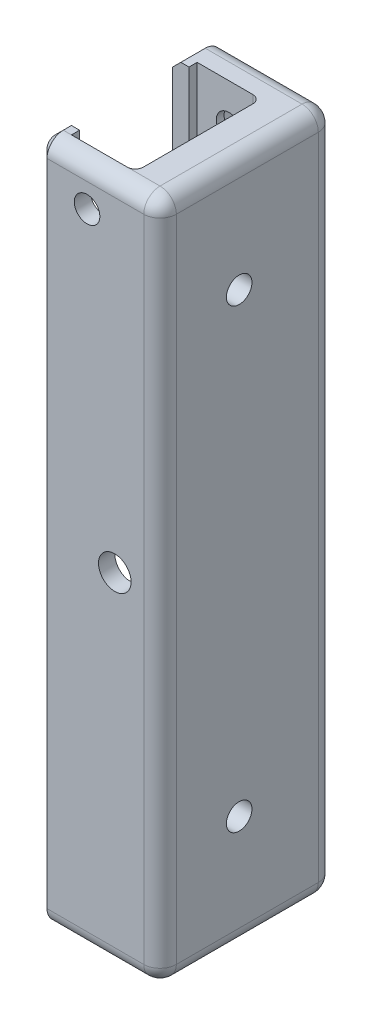
SolidWorks part; units mm, degrees
ref_plane "Front Plane" through (0, 0, 0) normal (0, 0, 1) x (1, 0, 0)
ref_plane "Top Plane" through (0, 0, 0) normal (0, 1, 0) x (1, 0, 0)
ref_plane "Right Plane" through (0, 0, 0) normal (1, 0, 0) x (0, 0, -1)
sketch "Sketch1" plane through (0, 0, 0) normal (0, 1, 0) x (1, 0, 0)
  line L0 (14.225, -12.25) -> (14.225, 12.25)
  line L1 (-6.225, -12.25) -> (6.225, -12.25) construction
  line L2 (-6.225, -12.25) -> (-6.225, 12.25) construction
  line L3 (-6.225, 12.25) -> (6.225, 12.25) construction
  line L4 (6.225, -12.25) -> (6.225, 12.25) construction
  line L5 (-6.225, -12.25) -> (6.225, 12.25) construction
  line L6 (-6.225, 12.25) -> (6.225, -12.25) construction
  line L7 (-6.225, 18.6) -> (6.225, 18.6)
  line L8 (-9.4, -15.425) -> (6.225, -15.425)
  line L9 (-9.4, -15.425) -> (-9.4, 12.25)
  line L10 (-9.4, 12.25) -> (-9.4, 18.6)
  line L11 (-9.4, 18.6) -> (-6.225, 18.6)
  line L12 (6.225, 18.6) -> (14.225, 18.6)
  line L13 (14.225, 18.6) -> (14.225, 12.25)
  line L14 (6.225, -15.425) -> (14.225, -15.425)
  line L15 (14.225, -15.425) -> (14.225, -12.25)
  point P0 (0, 0)
  dimension "D1" = 12.45
  dimension "D2" = 24.5
  dimension "D3" = 8
  dimension "D4" = 6.35
  dimension "D5" = 3.175
extrude "Boss-Extrude1" add sketch "Sketch1" along normal mid plane 133
sketch "Sketch2" plane through (0, 66.5, 0) normal (0, 1, 0) x (1, 0, 0)
  line L0 (14.225, 18.6) -> (-9.4, 18.6) construction
  line L1 (-6.225, -12.25) -> (6.225, -12.25)
  line L2 (-6.225, -12.25) -> (-6.225, 12.25)
  line L3 (-6.225, 12.25) -> (6.225, 12.25)
  line L4 (6.225, -12.25) -> (6.225, 12.25)
  line L5 (14.225, -15.425) -> (14.225, 18.6) construction
  line L6 (-9.4, -15.425) -> (14.225, -15.425) construction
  line L7 (-9.4, 18.6) -> (-9.4, -15.425) construction
  dimension "D1" = 6.35
  dimension "D2" = 8
  dimension "D3" = 3.175
  dimension "D4" = 3.175
extrude "Cut-Extrude1" cut sketch "Sketch2" against normal offset from surface (120.5 mm away) 54 up to plane "Top Plane" offset beyond the face yes
sketch "Sketch3" plane through (-9.4, 0, 0) normal (-1, 0, 0) x (0, 0, 1)
  line L0 (-18.6, 66.5) -> (15.425, 66.5) construction
  line L1 (10.6625, -50) -> (-10.6625, -50)
  line L2 (10.6625, -50) -> (10.6625, 66.5)
  line L3 (10.6625, 66.5) -> (-10.6625, 66.5)
  line L4 (-10.6625, -50) -> (-10.6625, 66.5)
  line L6 (15.425, 66.5) -> (15.425, -66.5) construction
  line L7 (-18.6, 66.5) -> (-18.6, -66.5) construction
  dimension "D1" = 50
  dimension "D2" = 4.7625
  dimension "D3" = 7.9375
extrude "Cut-Extrude2" cut sketch "Sketch3" against normal up to next
fillet "Fillet1" radius 1.5875 2 edges at (6.225, 6.25, 12.25) (6.225, 6.25, -12.25)
sketch "Sketch4" plane through (0, -66.5, 0) normal (0, -1, 0) x (1, 0, 0)
  line L1 (3.9687, 11.1125) -> (-3.9688, 11.1125)
  line L2 (3.9687, 11.1125) -> (3.9688, -11.1125)
  line L3 (3.9688, -11.1125) -> (-3.9687, -11.1125)
  line L4 (-3.9688, 11.1125) -> (-3.9687, -11.1125)
  line L5 (3.9687, 11.1125) -> (-3.9687, -11.1125) construction
  line L6 (3.9688, -11.1125) -> (-3.9688, 11.1125) construction
  point P0 (0, 0)
  dimension "D1" = 7.9375
  dimension "D2" = 22.225
extrude "Cut-Extrude3" cut sketch "Sketch4" against normal through all
fillet "Fillet2" radius 3.175 4 edges at (2.4125, 66.5, 15.425) (2.4125, 66.5, -18.6) (2.4125, -66.5, 15.425) (2.4125, -66.5, -18.6)
fillet "Fillet3" radius 1.5875 4 edges at (3.9687, -60.25, 11.1125) (-3.9688, -60.25, 11.1125) (-3.9687, -60.25, -11.1125) (3.9688, -60.25, -11.1125)
chamfer "Chamfer1" distance 1.5875 angle 45 9 edges at (-9.4, 66.5, 11.4563) (-9.4, 65.5701, 14.4951) (-9.4, 0, 15.425) (-9.4, -65.5701, 14.4951) (-9.4, 66.5, -13.0438) (-9.4, -66.5, -1.5875) (-9.4, 65.5701, -17.6701) (-9.4, -65.5701, -17.6701) (-9.4, 0, -18.6)
fillet "Fillet5" radius 3.175 2 edges at (-7.8125, -50, 10.6625) (-7.8125, -50, -10.6625)
sketch "Sketch5" plane through (0, 0, -18.6) normal (0, 0, -1) x (-1, 0, 0)
  line L0 (9.4, 63.325) -> (9.4, -63.325) construction
  circle A0 centre (-5.4, 0) radius 3.175
  point P4 (0, 0)
  point P5 (0, 0)
  dimension "D2" = 6.35
  dimension "D1" = 14.8
extrude "Cut-Extrude4" cut sketch "Sketch5" against normal through all
sketch "Sketch6" plane through (0, 0, 15.425) normal (0, 0, 1) x (1, 0, 0)
  circle A0 centre (5.4, 0) radius 5.5626
  dimension "D1" = 11.1252
extrude "Cut-Extrude5" cut sketch "Sketch6" against normal offset from surface (19.1216 mm away) 4.1465 from offset 12.7 up to face at (0.6146, 4.1667, -12.25) offset beyond the face yes offset against normal yes
fillet "Fillet6" radius 3.175 1 edges at (10.9626, 0, 2.725)
sketch "Sketch7" plane through (6.225, 0, 0) normal (-1, 0, 0) x (0, 0, 1)
  line L0 (0, -44.45) -> (0, 44.45) construction
  circle A0 centre (0, 44.45) radius 2.4892
  circle A1 centre (0, -44.45) radius 2.4892
  point P4 (0, 0)
  dimension "D1" = 4.9784
  dimension "D2" = 88.9
extrude "Cut-Extrude6" cut sketch "Sketch7" against normal through all
sketch "Sketch8" plane through (6.225, 0, 0) normal (-1, 0, 0) x (0, 0, 1)
  circle A0 centre (0, -44.45) radius 4.6355
  circle A1 centre (0, 44.45) radius 4.6355
  dimension "D1" = 9.271
extrude "Cut-Extrude7" cut sketch "Sketch8" against normal offset from surface (3.3591 mm away) 3.3592 up to face at (6.225, 44.45, 2.4892)
sketch "Sketch10" plane through (0, 0, -18.6) normal (0, 0, -1) x (-1, 0, 0)
  line L0 (0, -54) -> (0, 54) construction
  line L1 (0, 54) -> (0, 58.6625) construction
  line L2 (0, 58.6625) -> (0, 63.325) construction
  line L3 (7.8125, 63.325) -> (-14.225, 63.325) construction
  circle A0 centre (0, 58.6625) radius 2.4892
  point P4 (0, 0)
  dimension "D2" = 4.9784
  dimension "D1" = 108
extrude "Cut-Extrude8" cut sketch "Sketch10" against normal through all
sketch "Sketch11" plane through (0, 0, -18.6) normal (0, 0, -1) x (-1, 0, 0)
  circle A0 centre (0, 58.6625) radius 3.9688
  dimension "D1" = 7.9375
extrude "Cut-Extrude9" cut sketch "Sketch11" against normal blind 4.826
sketch "Sketch12" plane through (0, 0, -18.6) normal (0, 0, -1) x (-1, 0, 0)
  line L0 (-7.9, 21) -> (-4.7, 21) construction
  line L1 (-7.9, 21.625) -> (-4.7, 21.625)
  line L2 (-7.9, 20.375) -> (-4.7, 20.375)
  arc A0 (-7.9, 21.625) -> (-7.9, 20.375) centre (-7.9, 21) ccw
  arc A1 (-4.7, 20.375) -> (-4.7, 21.625) centre (-4.7, 21) ccw
  circle A2 centre (-5.4, 0) radius 3.175 construction
  point P2 (-6.3, 21)
  point P9 (-5.4228, 20.2261)
  point P10 (-4.7, 20.988)
  dimension "D4" = 0.625
  dimension "D1" = 21
  dimension "D2" = 2.5
  dimension "D3" = 3.2
extrude "Boss-Extrude3" add sketch "Sketch12" along normal blind 1.5
mirror "Mirror2" about plane through (0, 0, 0) normal (0, 1, 0) of "Boss-Extrude3"
fillet "Fillet7" radius 3.175 4 edges at (14.225, -66.5, -1.5875) (14.225, 66.5, -1.5875) (14.225, 0, 15.425) (14.225, 0, -18.6) tangent propagation no
